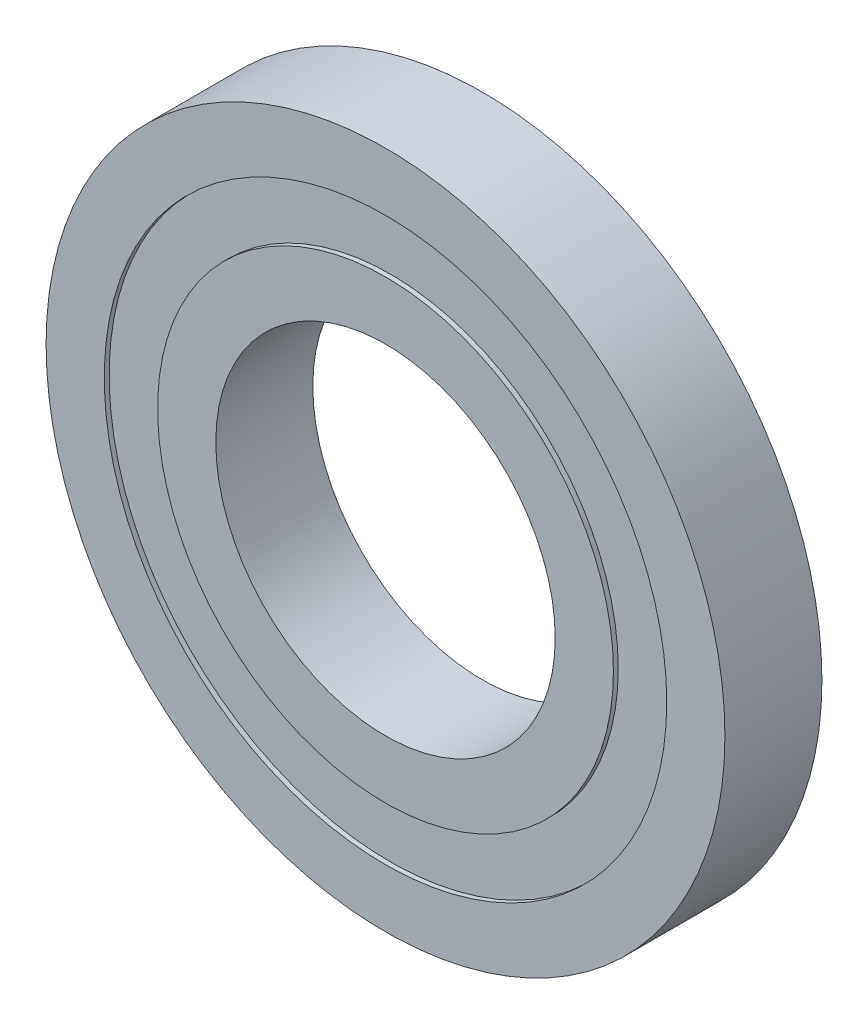
SolidWorks part; units mm, degrees
ref_plane "Front Plane" through (0, 0, 0) normal (1, 0, 0) x (0, 1, 0)
ref_plane "Top Plane" through (0, 0, 0) normal (0, 0, 1) x (0, 1, 0)
ref_plane "Right Plane" through (0, 0, 0) normal (0, 1, 0) x (-1, 0, 0)
sketch "Sketch1" plane through (0, 0, 0) normal (0, 0, 1) x (0, 1, 0)
  circle A0 centre (0, 0) radius 17.5
  circle A1 centre (0, 0) radius 35
  circle A2 centre (0, 0) radius 29
  circle A3 centre (0, 0) radius 23.5
  dimension "D1" = 70
  dimension "D2" = 35
  dimension "D3" = 6
  dimension "D4" = 6
extrude "Boss-Extrude1" add sketch "Sketch1" along normal blind 10 contours A3 A0 | A1 A2 region at (0, -34.0101, 0) region at (0, -22.8353, 0)
extrude "Boss-Extrude2" add sketch "Sketch1<3>" along normal blind 9 from offset 0.5 contours A2 A3 region at (0, -28.1798, 0)
sketch "Sketch1<3>" plane through (0, 0, 0) normal (0, 0, 1) x (0, 1, 0) same geometry as "Sketch1"
